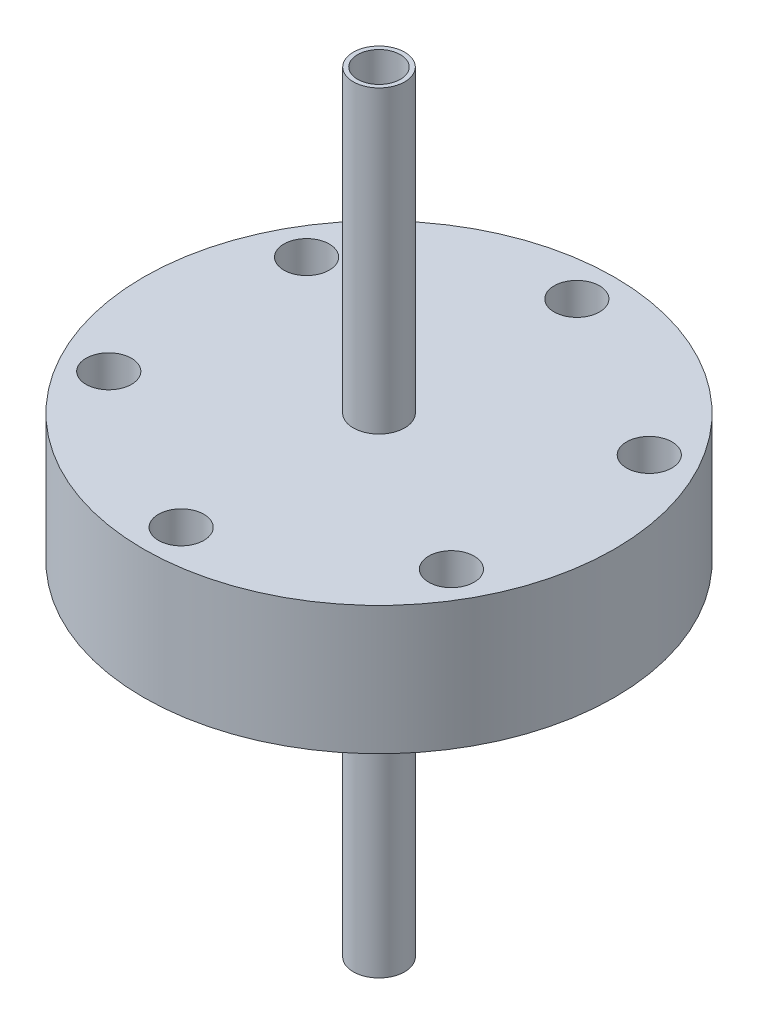
SolidWorks part; units mm, degrees
ref_plane "Front Plane" through (0, 0, 0) normal (0, 0, 1) x (1, 0, 0)
ref_plane "Top Plane" through (0, 0, 0) normal (0, 1, 0) x (1, 0, 0)
ref_plane "Right Plane" through (0, 0, 0) normal (1, 0, 0) x (0, 0, -1)
sketch "Sketch1" plane through (0, 0, 0) normal (0, 1, 0) x (1, 0, 0)
  circle A0 centre (0, 0) radius 34.925
  dimension "D1" = 69.85
extrude "Extrude1" add sketch "Sketch1" along normal blind 19.05
sketch "Sketch2" plane through (0, 0, 0) normal (0, 1, 0) x (1, 0, 0)
  circle A0 centre (0, 0) radius 3.175
  dimension "D1" = 6.35
extrude "Cut-Extrude1" cut sketch "Sketch2" along normal through all
sketch "Sketch3" plane through (0, 0, 0) normal (0, 1, 0) x (1, 0, 0)
  circle A0 centre (0, 29.337) radius 3.3655
  dimension "D1" = 6.731
  dimension "D2" = 29.337
extrude "Cut-Extrude2" cut sketch "Sketch3" along normal through all
ref_axis "Axis1" through (0, 35.8582, 0) along (0, -1, 0)
pattern_circular "CirPattern1" count 6 over 360 about axis through (0, 35.8582, 0) along (0, -1, 0) of "Cut-Extrude2"
sketch "Sketch4" plane through (0, 0, 0) normal (0, 1, 0) x (1, 0, 0)
  line L0 (0, 0) -> (0, 16.8619)
ref_plane "Plane1" through (0, 0, 0) normal (0, -1, 0) x (1, 0, 0)
sketch "Sketch5" plane through (0, 0, 0) normal (0, -1, 0) x (1, 0, 0)
  circle A0 centre (0, 0) radius 3.175
  dimension "D1" = 6.35
extrude "Extrude-Thin1" add sketch "Sketch5" along normal blind 50.8 and the other way blind 63.5 thin thin type one direction wall 0.635
